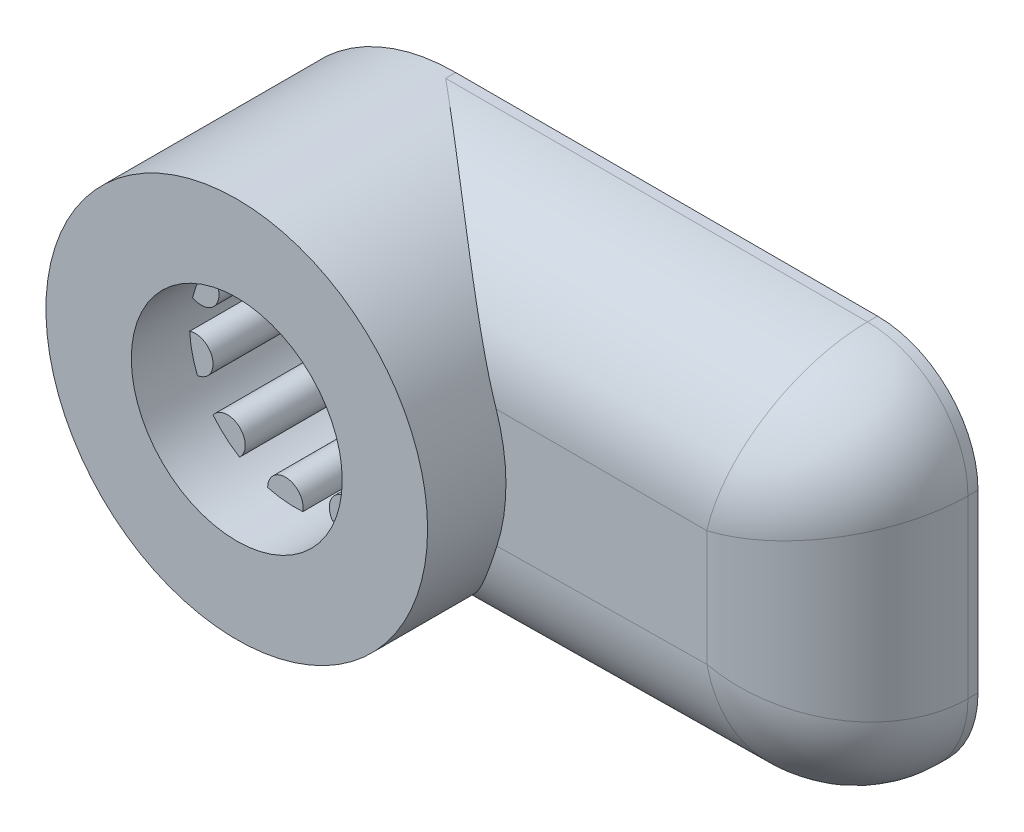
SolidWorks part; units mm, degrees
ref_plane "Спереди" through (0, 0, 0) normal (0, 0, 1) x (1, 0, 0)
ref_plane "Сверху" through (0, 0, 0) normal (0, 1, 0) x (1, 0, 0)
ref_plane "Справа" through (0, 0, 0) normal (1, 0, 0) x (0, 0, -1)
sketch "Эскиз1" plane through (0, 0, 0) normal (0, 0, 1) x (1, 0, 0)
  circle A0 centre (0, 0) radius 9.5
  circle A1 centre (0, 0) radius 2.3 construction
  dimension "D1" = 19
  dimension "D2" = 4.6
extrude "Бобышка-Вытянуть1" add sketch "Эскиз1" along normal blind 8
sketch "Эскиз2" plane through (0, 0, 8) normal (0, 0, 1) x (1, 0, 0)
  circle A0 centre (0, 0) radius 5.25
  dimension "D1" = 10.5
extrude "Вырез-Вытянуть1" cut sketch "Эскиз2" against normal blind 5
sketch "Эскиз4" plane through (0, 0, 0) normal (0, 0, -1) x (-1, 0, 0)
  line L0 (0, 9.5) -> (-21, 9.5)
  line L1 (0, -9.5) -> (-21.0606, -9.2447)
  line L2 (-26, -4.2451) -> (-26, 4.5)
  line L3 (-9.5, 0) -> (-6.5, 0) construction
  circle A1 centre (0, 0) radius 9.5 construction
  arc A2 (-21.0606, -9.2447) -> (-26, -4.2451) centre (-21, -4.2451) cw
  arc A3 (-21, 9.5) -> (-26, 4.5) centre (-21, 4.5) ccw
  arc A4 (0, -9.5) -> (0, 9.5) centre (3.6939, 0) cw
  point P11 (-26, 9.5)
  dimension "D2" = 5
  dimension "D1" = 26
extrude "Бобышка-Вытянуть2" add sketch "Эскиз4" against normal blind 7
fillet "Скругление1" radius 6.5 5 edges at (24.5569, -7.7591, 7) (26, 0.1275, 7) (24.5355, 8.0355, 7) (10.5, 9.5, 7)
sketch "Эскиз5" plane through (0, 0, 8) normal (0, 0, 1) x (1, 0, 0)
  line L1 (0.5594, 3.6336) -> (0.7988, 5.1889) construction
  line L2 (0.5594, 3.6336) -> (0.4054, 2.6336) construction
  line L4 (-0.3897, 5.2355) -> (1.3603, 5.0707) construction
  line L5 (0.4853, 5.1531) -> (0.408, 4.1837) construction
  arc A1 (-0.3897, 5.2355) -> (1.3603, 5.0707) centre (0.4769, 5.0638) ccw
  circle A3 centre (0, 0) radius 5.25 construction
  arc A5 (-0.3897, 5.2355) -> (1.3603, 5.0707) centre (0.4175, 4.4329) cw
  dimension "D1" = 1.75
  dimension "D2" = 1
extrude "Бобышка-Вытянуть4" add sketch "Эскиз5" against normal up to surface (5 mm away) up to face at (5.25, 0, 3)
pattern_circular "Круговой массив4" count 10 over 360 about axis through (0, 0, 3) along (0, 0, 1) of "Бобышка-Вытянуть4"
sketch "Эскиз6" plane through (0, 0, 8) normal (0, 0, 1) x (1, 0, 0)
  circle A0 centre (0, 0) radius 9.5
  circle A1 centre (0, 0) radius 5.25
  arc A2 (2.7621, 4.4647) -> (1.3603, 5.0707) centre (0, 0) ccw construction
extrude "Бобышка-Вытянуть5" add sketch "Эскиз6" along normal blind 2.9
